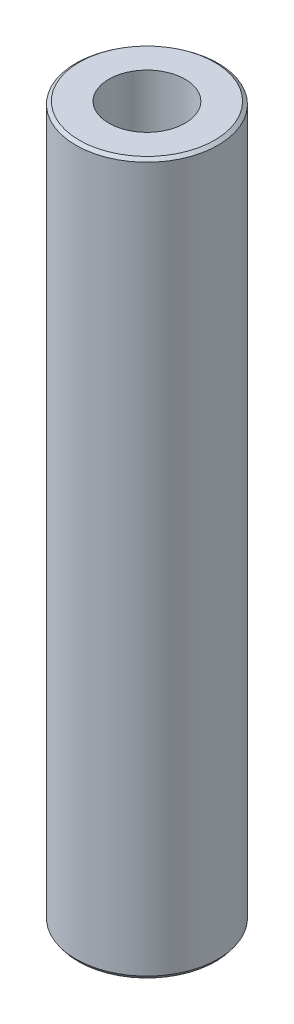
SolidWorks part; units mm, degrees
ref_plane "Front Plane" through (0, 0, 0) normal (0, 0, 1) x (1, 0, 0)
ref_plane "Top Plane" through (0, 0, 0) normal (0, 1, 0) x (1, 0, 0)
ref_plane "Right Plane" through (0, 0, 0) normal (1, 0, 0) x (0, 0, -1)
sketch "Sketch1" plane through (0, 0, 0) normal (0, 1, 0) x (1, 0, 0)
  circle A0 centre (0, 0) radius 60
  dimension "SHAFT_OD" = 120
extrude "Boss-Extrude1" add sketch "Sketch1" along normal blind 600
sketch "Sketch2" plane through (0, 0, 0) normal (0, 1, 0) x (1, 0, 0)
  circle A0 centre (0, 0) radius 32.1893
  dimension "BORE_D" = 64.3785
extrude "Cut-Extrude1" cut sketch "Sketch2" along normal through all
chamfer "Chamfer1" distance 2.2014 angle 53.059 2 edges at (0, 600, 60) (0, 0, 60) first distance on face at (0, 600, 60) first distance on face at (0, 0, 32.1893)
